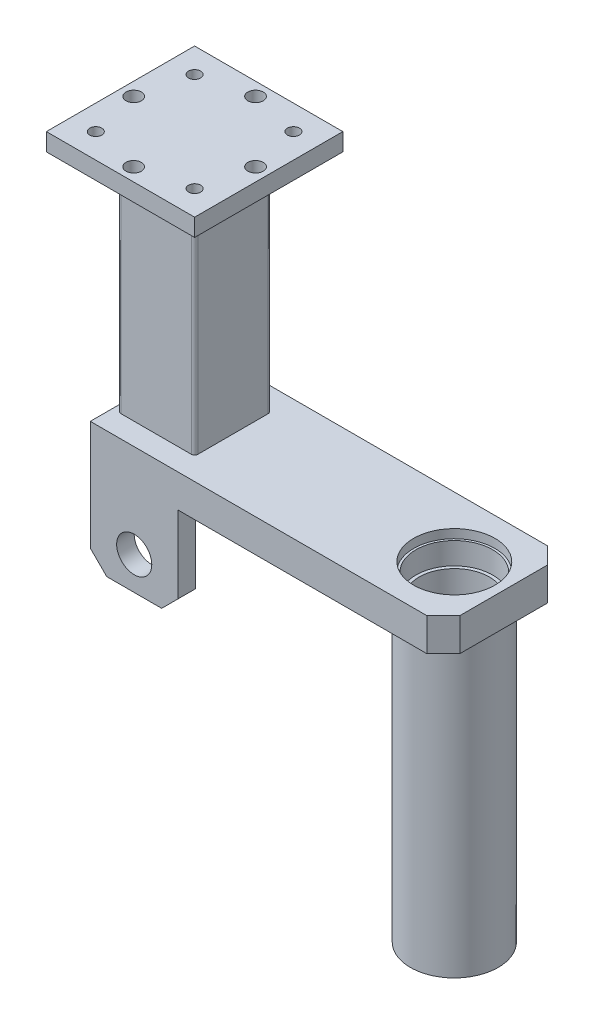
SolidWorks part; units mm, degrees
material "Structural Steel"
ref_plane "Piano frontale" through (0, 0, 0) normal (0, 0, 1) x (1, 0, 0)
ref_plane "Piano superiore" through (0, 0, 0) normal (0, 1, 0) x (1, 0, 0)
ref_plane "Piano destro" through (0, 0, 0) normal (1, 0, 0) x (0, 0, -1)
sketch "Schizzo1" plane through (0, 0, 0) normal (0, 1, 0) x (1, 0, 0)
  line L0 (0, 67.5) -> (92.9115, 67.5) construction
  line L1 (0, 0) -> (135, 0)
  line L2 (0, 0) -> (0, 135)
  line L3 (0, 135) -> (135, 135)
  line L4 (135, 0) -> (135, 135)
  line L5 (67.5, 135) -> (67.5, 66.7214) construction
  circle A0 centre (22.5, 112.5) radius 5.5
  circle A1 centre (112.5, 112.5) radius 5.5
  circle A2 centre (112.5, 22.5) radius 5.5
  circle A3 centre (22.5, 22.5) radius 5.5
  dimension "D3" = 11
  dimension "D1" = 135
  dimension "D2" = 135
  dimension "D4" = 45
  dimension "D5" = 45
extrude "Estrusione1" add sketch "Schizzo1" along normal blind 16
sketch "Schizzo2" plane through (0, 0, 0) normal (0, -1, 0) x (1, 0, 0)
  line L0 (0, 0) -> (135, 0) construction
  line L1 (35.5, -32.5) -> (99.5, -32.5)
  line L2 (32.5, -35.5) -> (32.5, -99.5)
  line L3 (35.5, -102.5) -> (99.5, -102.5)
  line L4 (102.5, -35.5) -> (102.5, -99.5)
  line L5 (0, -135) -> (0, 0) construction
  arc A0 (35.5, -32.5) -> (32.5, -35.5) centre (35.5, -35.5) ccw
  arc A1 (99.5, -32.5) -> (102.5, -35.5) centre (99.5, -35.5) cw
  arc A2 (99.5, -102.5) -> (102.5, -99.5) centre (99.5, -99.5) ccw
  arc A3 (32.5, -99.5) -> (35.5, -102.5) centre (35.5, -99.5) ccw
  point P10 (32.5, -32.5)
  point P13 (102.5, -32.5)
  point P18 (32.5, -102.5)
  dimension "D5" = 3
  dimension "D1" = 70
  dimension "D2" = 70
  dimension "D3" = 32.5
  dimension "D4" = 32.5
extrude "Estrusione-Sottile1" add sketch "Schizzo2" along normal blind 205 thin thin type one direction reverse wall 4
sketch "Schizzo3" plane through (0, -205, 0) normal (0, -1, 0) x (1, 0, 0)
  line L0 (27.5, -12.5) -> (27.5, -122.5)
  line L1 (32.5, -35.5) -> (32.5, -99.5) construction
  line L2 (27.5, -12.5) -> (349, -12.5)
  line L3 (99.5, -32.5) -> (35.5, -32.5) construction
  line L4 (27.5, -122.5) -> (349, -122.5)
  line L5 (35.5, -102.5) -> (99.5, -102.5) construction
  line L6 (349, -12.5) -> (349, -122.5)
  line L7 (135, 0) -> (135, -135) construction
  dimension "D1" = 5
  dimension "D2" = 20
  dimension "D3" = 20
  dimension "D4" = 214
extrude "Estrusione2" add sketch "Schizzo3" along normal blind 30
sketch "Schizzo4" plane through (0, -235, 0) normal (0, -1, 0) x (1, 0, 0)
  line L1 (349, -12.5) -> (27.5, -12.5) construction
  line L3 (22.5, -22.5) -> (112.5, -22.5) construction
  line L4 (22.5, -22.5) -> (22.5, -112.5) construction
  line L5 (22.5, -112.5) -> (112.5, -112.5) construction
  line L6 (112.5, -22.5) -> (112.5, -112.5) construction
  line L7 (22.5, -22.5) -> (112.5, -112.5) construction
  line L8 (22.5, -112.5) -> (112.5, -22.5) construction
  circle A0 centre (304, -67.5) radius 40
  point P8 (67.5, -67.5)
  dimension "D1" = 80
  dimension "D2" = 236.5
  dimension "D3" = 55
extrude "Estrusione3" add sketch "Schizzo4" along normal blind 270
sketch "Schizzo6" plane through (0, -505, 0) normal (0, -1, 0) x (1, 0, 0)
  circle A0 centre (304, -67.5) radius 32
extrude "Estrusione4" cut sketch "Schizzo6" against normal through all
sketch "Schizzo7" plane through (0, -505, 0) normal (0, -1, 0) x (1, 0, 0)
  circle A0 centre (304, -67.5) radius 35
extrude "Estrusione5" cut sketch "Schizzo7" against normal blind 28
sketch "Schizzo8" plane through (0, -205, 0) normal (0, 1, 0) x (1, 0, 0)
  circle A0 centre (304, 67.5) radius 35
extrude "Estrusione6" cut sketch "Schizzo8" against normal blind 28
sketch "Schizzo9" plane through (0, -235, 0) normal (0, -1, 0) x (1, 0, 0)
  line L0 (67.5, 25.4546) -> (67.5, -152.5502) construction
  line L1 (27.5, -12.5) -> (27.5, -122.5) construction
  line L2 (293.8417, -67.5) -> (-53.2214, -67.5) construction
  line L4 (107.5, -122.5) -> (107.5, -106.5)
  line L5 (27.5, -12.5) -> (107.5, -12.5)
  line L6 (27.5, -12.5) -> (27.5, -28.5)
  line L7 (27.5, -28.5) -> (107.5, -28.5)
  line L8 (107.5, -12.5) -> (107.5, -28.5)
  line L9 (27.5, -106.5) -> (107.5, -106.5)
  line L10 (27.5, -122.5) -> (27.5, -106.5)
  line L11 (27.5, -122.5) -> (107.5, -122.5)
  line L12 (349, -12.5) -> (27.5, -12.5) construction
  dimension "D1" = 40
  dimension "D2" = 55
  dimension "D3" = 80
  dimension "D4" = 16
extrude "Estrusione7" add sketch "Schizzo9" along normal blind 85
sketch "Schizzo10" plane through (0, 0, -12.5) normal (0, 0, 1) x (1, 0, 0)
  line L1 (349, -235) -> (107.5, -235) construction
  line L2 (107.5, -320) -> (107.5, -235) construction
  circle A0 centre (67.5, -290) radius 16
  dimension "D1" = 55
  dimension "D2" = 32
  dimension "D3" = 40
extrude "Estrusione8" cut sketch "Schizzo10" against normal blind 40
sketch "Schizzo11" plane through (0, 0, -122.5) normal (0, 0, -1) x (-1, 0, 0)
  line L0 (-107.5, -235) -> (-349, -235) construction
  line L1 (-107.5, -320) -> (-107.5, -235) construction
  circle A0 centre (-67.5, -290) radius 17.5
  dimension "D1" = 35
  dimension "D2" = 55
  dimension "D3" = 40
extrude "Estrusione9" cut sketch "Schizzo11" against normal blind 40
chamfer "Smusso1" distance 15 angle 45 6 edges at (349, -220, -12.5) (349, -220, -122.5) (27.5, -320, -20.5) (107.5, -320, -20.5) (27.5, -320, -114.5) (107.5, -320, -114.5)
sketch "Schizzo12" plane through (0, -505, 0) normal (0, -1, 0) x (1, 0, 0)
  circle A0 centre (304, -67.5) radius 37
extrude "Estrusione10" cut sketch "Schizzo12" against normal blind 8
sketch "Schizzo13" plane through (0, -205, 0) normal (0, 1, 0) x (1, 0, 0)
  circle A0 centre (304, 67.5) radius 37
extrude "Estrusione11" cut sketch "Schizzo13" against normal blind 8
hole_wizard "M16 Tapped Hole1" positions "Sketch1" profile "Sketch2" tap size "M16" standard "ISO"
sketch "Sketch1" plane through (0, 16, 0) normal (0, 1, 0) x (-1, 0, 0)
  line L0 (-135, -135) -> (0, -135) construction
  line L1 (0, -135) -> (0, 0) construction
  line L2 (-135, 0) -> (-135, -135) construction
  line L3 (0, 0) -> (-135, 0) construction
  line L4 (-1000, -67.5) -> (49000, -67.5) construction
  line L5 (-67.5, -1000) -> (-67.5, 49000) construction
  point P0 (-67.5, -123)
  point P7 (-12, -67.5)
  point P9 (-67.5, -12)
  point P11 (-123, -67.5)
  point P21 (0, -67.5)
  point P26 (-67.5, 0)
  dimension "D1" = 12
  dimension "D2" = 67.5
  dimension "D3" = 12
  dimension "D4" = 12
  dimension "D5" = 12
sketch "Sketch2" plane through (67.5, 16, -123) normal (1, 0, 0) x (0, 0, 1)
  line L0 (0, 0) -> (0, 46.206)
  line L1 (0, 46.206) -> (7, 42)
  line L2 (7, 42) -> (7, 0)
  line L5 (7, 0) -> (0, 0)
  line L10 (0, 46.206) -> (-7, 42) construction
  line L11 (0, -6.35) -> (0, 107.95) construction
  dimension "Tap Drill Dia." = 14
  dimension "Tap Drill Depth" = 42
  dimension "Drill Angle" = 118
cosmetic thread "Cosmetic Thread1" parameters "D1"=16, "D2"=16
cosmetic thread "Cosmetic Thread2" parameters "D1"=16, "D2"=16
cosmetic thread "Cosmetic Thread3" parameters "D1"=16, "D2"=16
cosmetic thread "Cosmetic Thread4" parameters "D1"=16, "D2"=16
ref_axis "Assi1" through (304, -233, -67.5) along (0, -1, 0)
